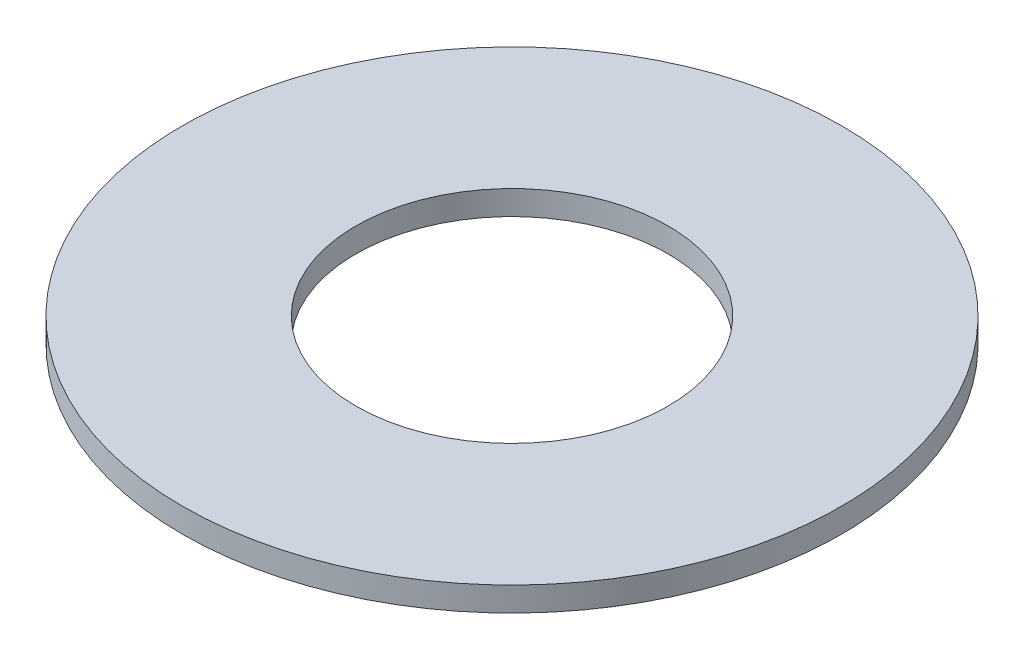
SolidWorks part; units mm, degrees
ref_plane "Front Plane" through (0, 0, 0) normal (0, 0, 1) x (1, 0, 0)
ref_plane "Top Plane" through (0, 0, 0) normal (0, 1, 0) x (1, 0, 0)
ref_plane "Right Plane" through (0, 0, 0) normal (1, 0, 0) x (0, 0, -1)
sketch "Sketch1" plane through (0, 0, 0) normal (0, 1, 0) x (1, 0, 0)
  circle A0 centre (0, 0) radius 95
  dimension "FLANGE_OD" = 190
extrude "Boss-Extrude1" add sketch "Sketch1" along normal blind 7
sketch "Sketch2" plane through (0, 0, 0) normal (0, 1, 0) x (1, 0, 0)
  circle A0 centre (0, 0) radius 45
  dimension "BORE_D" = 90
extrude "Cut-Extrude1" cut sketch "Sketch2" along normal through all
sketch "Sketch3" plane through (0, 7, 0) normal (0, 1, 0) x (1, 0, 0)
  circle A0 centre (0, 0) radius 26.6581 construction
  circle A1 centre (-26.6581, 0) radius 5.9542
  dimension "BOLT_D" = 11.9085
  dimension "BOLT_PCD" = 53.3161
extrude "Cut-Extrude2" cut sketch "Sketch3" against normal blind 6.4379 rebuild error yes
pattern_circular "CirPattern1" count 8 over 360 rebuild error yes
